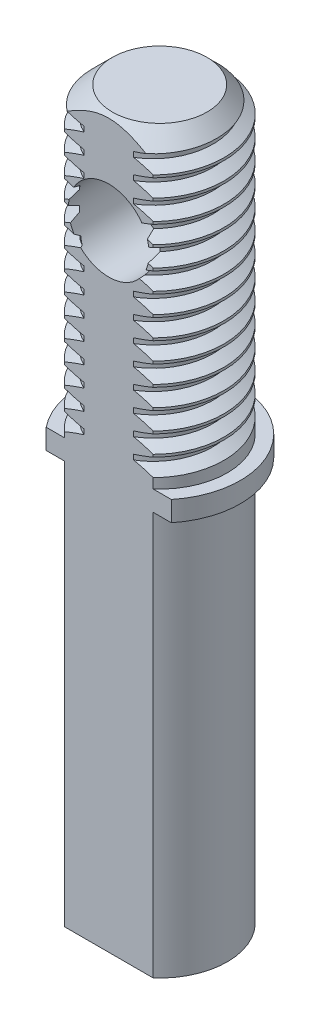
SolidWorks part; units mm, degrees
ref_plane "Спереди" through (0, 0, 0) normal (0, 0, 1) x (1, 0, 0)
ref_plane "Сверху" through (0, 0, 0) normal (0, 1, 0) x (1, 0, 0)
ref_plane "Справа" through (0, 0, 0) normal (1, 0, 0) x (0, 0, -1)
sketch "Эскиз1" plane through (0, 0, 0) normal (0, 1, 0) x (1, 0, 0)
  circle A0 centre (0, 0) radius 3.35
  dimension "D1" = 6.7
extrude "Бобышка-Вытянуть1" add sketch "Эскиз1" along normal blind 15
chamfer "Фаска1" distance 1 angle 45 1 edges at (0, 15, 3.35)
thread "Резьба1" pitch 1 method cut profile "Профиль резьбы1" start angle 0, offset 1, length 14, pitch 1, diameter 6.7
ref_plane "Плоскость4" through (-3.35, 15, 0) normal (0, 0, 1) x (-1, 0, 0)
sketch "Профиль резьбы1" plane through (-3.35, 15, 0) normal (0, 0, 1) x (-1, 0, 0)
  line L0 (0, 0) -> (0, 1) construction
  line L11 (0, 0) -> (0, 0.875)
  line L12 (0, 0.875) -> (-0.5413, 0.5625)
  line L13 (-0.5413, 0.5625) -> (-0.5413, 0.3125)
  line L15 (-0.5413, 0.3125) -> (0, 0)
  line L17 (-0.5413, 0.4375) -> (0, 0.4375) construction
  point P2 (0, 0)
  dimension "Pitch" = 1
  dimension "Profile_Angle" = 60
  dimension "Profile_Land" = 0.25
  dimension "Profile_Height" = 0.5413
sketch "Эскиз5" plane through (0, 0, 0) normal (0, -1, 0) x (1, 0, 0)
  circle A0 centre (0, 0) radius 4
  dimension "D1" = 8
extrude "Бобышка-Вытянуть2" add sketch "Эскиз5" along normal blind 1
sketch "Эскиз6" plane through (0, -1, 0) normal (0, -1, 0) x (1, 0, 0)
  circle A0 centre (0, 0) radius 3.35
  dimension "D1" = 6.7
extrude "Бобышка-Вытянуть3" add sketch "Эскиз6" along normal blind 20
sketch "Эскиз7" plane through (0, 0, 0) normal (0, 0, 1) x (1, 0, 0)
  line L0 (0, 18.4895) -> (0, -5.1776) construction
  line L1 (2.35, 15) -> (-2.35, 15) construction
  circle A0 centre (0, 10) radius 2
  dimension "D1" = 4
  dimension "D2" = 5
extrude "Вырез-Вытянуть1" cut sketch "Эскиз7" against normal through all both and the other way through all
sketch "Эскиз8" plane through (0, -21, 0) normal (0, -1, 0) x (1, 0, 0)
  line L1 (-3.3746, 4.0257) -> (3.6612, 4.0257)
  line L2 (-3.3746, 4.0257) -> (-3.3746, 2.5257)
  line L3 (-3.3746, 2.5257) -> (3.6612, 2.5257)
  line L4 (3.6612, 4.0257) -> (3.6612, 2.5257)
  dimension "D1" = 1.5
extrude "Вырез-Вытянуть2" cut sketch "Эскиз8" against normal through all
